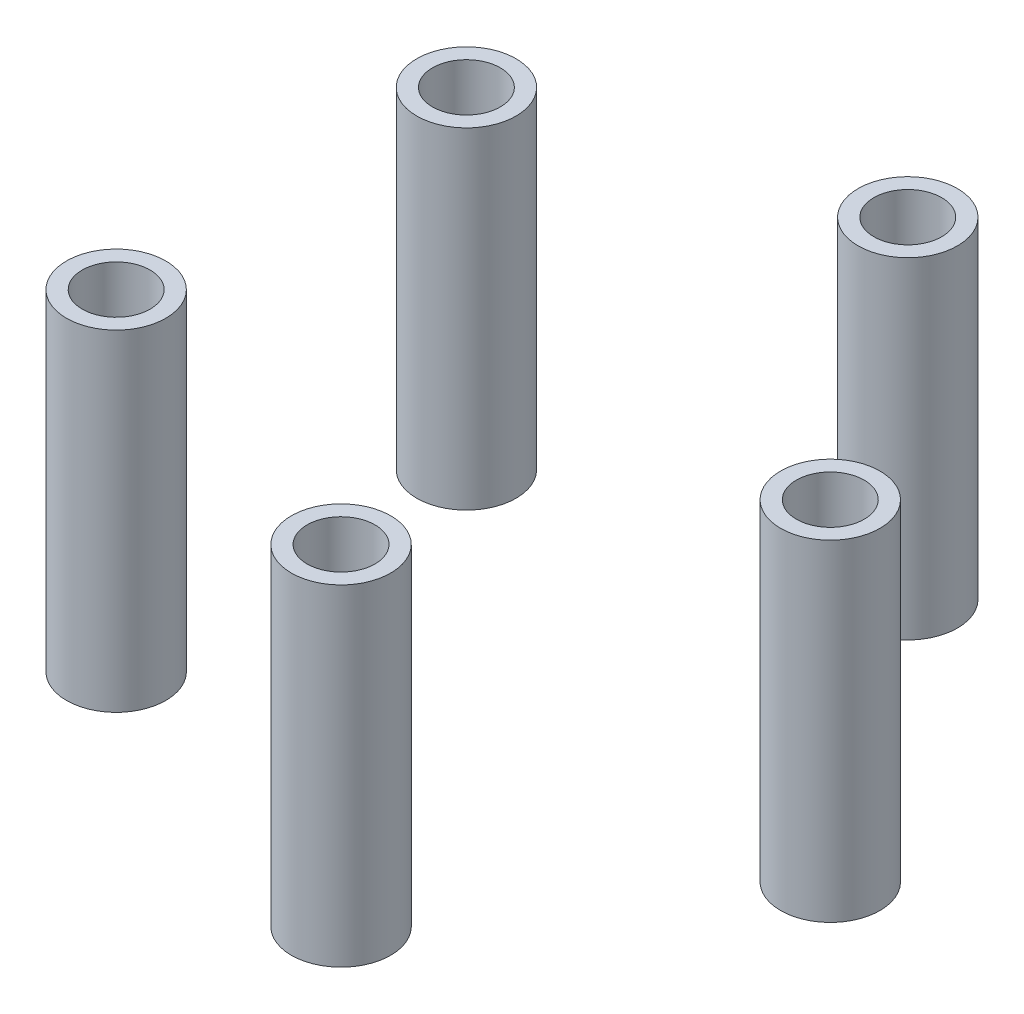
SolidWorks part; units mm, degrees
ref_plane "Front Plane" through (0, 0, 0) normal (0, 0, 1) x (1, 0, 0)
ref_plane "Top Plane" through (0, 0, 0) normal (0, 1, 0) x (1, 0, 0)
ref_plane "Right Plane" through (0, 0, 0) normal (1, 0, 0) x (0, 0, -1)
sketch "Sketch1" plane through (0, 0, 0) normal (0, 1, 0) x (1, 0, 0)
  line L0 (-18.8623, 10.5801) -> (-12.6623, 10.5801) construction
  line L1 (1.2623, 17.119) -> (7.4623, 17.119) construction
  line L2 (13.7, 0) -> (19.9, 0) construction
  line L3 (1.2623, -17.119) -> (7.4623, -17.119) construction
  line L4 (-18.8623, -10.5801) -> (-12.6623, -10.5801) construction
  circle A0 centre (-14.5623, 10.5801) radius 4.3 construction
  circle A1 centre (-16.9623, 10.5801) radius 4.3 construction
  circle A4 centre (5.5623, 17.119) radius 4.3 construction
  circle A5 centre (3.1623, 17.119) radius 4.3 construction
  circle A6 centre (18, 0) radius 4.3 construction
  circle A7 centre (15.6, 0) radius 4.3 construction
  circle A8 centre (5.5623, -17.119) radius 4.3 construction
  circle A9 centre (3.1623, -17.119) radius 4.3 construction
  circle A10 centre (-14.5623, -10.5801) radius 4.3 construction
  circle A11 centre (-16.9623, -10.5801) radius 4.3 construction
  circle A12 centre (-15.7623, -10.5801) radius 3
  circle A13 centre (4.3623, -17.119) radius 3
  circle A14 centre (16.8, 0) radius 3
  circle A15 centre (16.8, 0) radius 2.05
  circle A16 centre (4.3623, -17.119) radius 2.05
  circle A17 centre (-15.7623, -10.5801) radius 2.05
  circle A18 centre (-15.7623, 10.5801) radius 2.05
  circle A19 centre (-15.7623, 10.5801) radius 3
  circle A20 centre (4.3623, 17.119) radius 3
  circle A21 centre (4.3623, 17.119) radius 2.05
  dimension "D1" = 6
extrude "Boss-Extrude1" add sketch "Sketch1" along normal blind 10 and the other way blind 10
